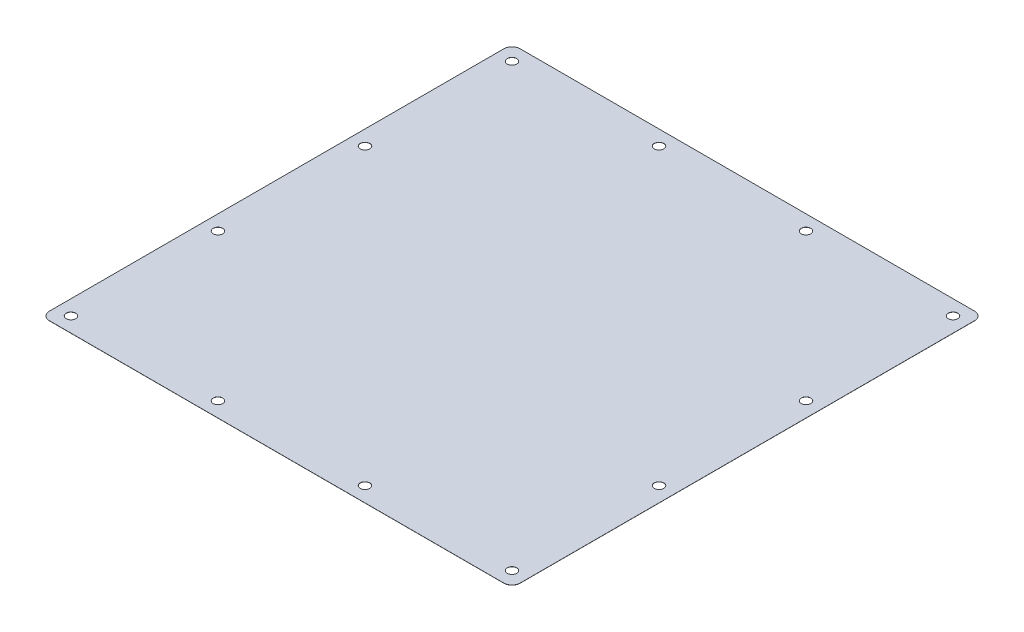
SolidWorks part; units mm, degrees
note: The reader was unsure of these and kept them because the rebuilt part matched: thickness of "Base-Flange1", "Sheet-Metal1", "Sheet-Metal5".
material "AISI 321 Annealed Stainless Steel (SS)"
ref_plane "Front Plane" through (0, 0, 0) normal (0, 0, 1) x (1, 0, 0)
ref_plane "Top Plane" through (0, 0, 0) normal (0, 1, 0) x (1, 0, 0)
ref_plane "Right Plane" through (0, 0, 0) normal (1, 0, 0) x (0, 0, -1)
sketch "Sketch2" plane through (0, 0, 0) normal (0, 1, 0) x (1, 0, 0)
  line L1 (3.175, 0) -> (177.038, 0)
  line L2 (0, 3.175) -> (0, 177.038)
  line L3 (3.175, 180.213) -> (177.038, 180.213)
  line L4 (180.213, 3.175) -> (180.213, 177.038)
  arc A0 (180.213, 3.175) -> (177.038, 0) centre (177.038, 3.175) cw
  arc A1 (180.213, 177.038) -> (177.038, 180.213) centre (177.038, 177.038) ccw
  arc A2 (3.175, 180.213) -> (0, 177.038) centre (3.175, 177.038) ccw
  arc A3 (3.175, 0) -> (0, 3.175) centre (3.175, 3.175) cw
  point P9 (180.213, 180.213)
  point P12 (0, 180.213)
  point P15 (0, 0)
  dimension "D3" = 3.175
  dimension "D1" = 180.213
  dimension "D2" = 180.213
base flange "Base-Flange1" sketch "Sketch2" thickness 0.0508 reverse thickness direction no parameters "D1"=1.5875
hole_wizard "#6 Clearance Hole1" positions "Sketch9" profile "Sketch8" hole size "#6" standard "ANSI Inch" end condition through all
sketch "Sketch9" plane through (0, 0, 0) normal (0, 1, 0) x (1, 0, 0)
  line L3 (180.213, 3.175) -> (180.213, 177.038) construction
  line L4 (180.213, 174.498) -> (0, 174.498) construction
  line L16 (90.1065, 0) -> (90.1065, 180.213) construction
  line L23 (14.5288, 11.3538) -> (11.3538, 11.3538) construction
  line L24 (3.175, 0) -> (177.038, 0) construction
  line L25 (177.038, 180.213) -> (3.175, 180.213) construction
  line L26 (180.213, 5.715) -> (0, 5.715) construction
  line L27 (180.213, 3.175) -> (180.213, 177.038) construction
  line L28 (0, 177.038) -> (0, 3.175) construction
  line L30 (174.498, 0) -> (174.498, 180.213) construction
  point P157 (118.237, 5.715)
  point P159 (174.498, 5.715)
  point P161 (174.498, 61.976)
  point P163 (174.498, 118.237)
  point P165 (174.498, 174.498)
  point P167 (118.237, 174.498)
  point P175 (61.976, 174.498)
  point P176 (5.715, 174.498)
  point P177 (5.715, 118.237)
  point P178 (5.715, 61.976)
  point P179 (5.715, 5.715)
  point P180 (61.976, 5.715)
  dimension "D2" = 56.261
  dimension "D7" = 5.715
  dimension "D8" = 5.715
  dimension "D9" = 56.261
  dimension "D10" = 56.261
  dimension "D11" = 56.261
  dimension "D12" = 56.261
sketch "Sketch8" plane through (118.237, 0, -5.715) normal (1, 0, 0) x (0, 0, 1)
  line L0 (0, 0) -> (0, 0.0508)
  line L1 (0, 0.0508) -> (1.8288, 0.0508)
  line L2 (1.8288, 0.0508) -> (1.8288, 0)
  line L5 (1.8288, 0) -> (0, 0)
  line L11 (0, -6.35) -> (0, 107.95) construction
  dimension "Thru Hole Dia." = 3.6576
  dimension "Thru Hole Depth" = 0.0508
sketch "Bend-Lines1" [suppressed] plane through (0, 0, 0) normal (0, 1, 0) x (1, 0, 0)
sketch "Bounding-Box1" [suppressed] plane through (0, 0, 0) normal (0, 1, 0) x (1, 0, 0)
sheet metal parameters "Sheet-Metal1" thickness 0.0508 parameters "D1"=1.5875
flat pattern "Flat-Pattern1" [suppressed]
sketch "Bend-Lines2" plane through (0, 0, 0) normal (0, 1, 0) x (1, 0, 0)
sketch "Bounding-Box2" [suppressed] plane through (0, 0, 0) normal (0, 1, 0) x (1, 0, 0)
sheet metal parameters "Sheet-Metal5" thickness 0.0508 parameters "D1"=1.5875, "D7"=0.7937
flat pattern "Flat-Pattern1"
sketch "Bend-Lines2" plane through (0, 0, 0) normal (0, 1, 0) x (1, 0, 0)
sketch3d "Bounding-Box2" [suppressed]
  line L0 (-177.038, -3.175, 0) -> (-177.038, 177.038, 0) construction
  line L1 (3.175, -3.175, 0) -> (3.175, 177.038, 0) construction
  line L2 (-177.038, -3.175, 0) -> (3.175, -3.175, 0) construction
  line L3 (-177.038, 177.038, 0) -> (3.175, 177.038, 0) construction
